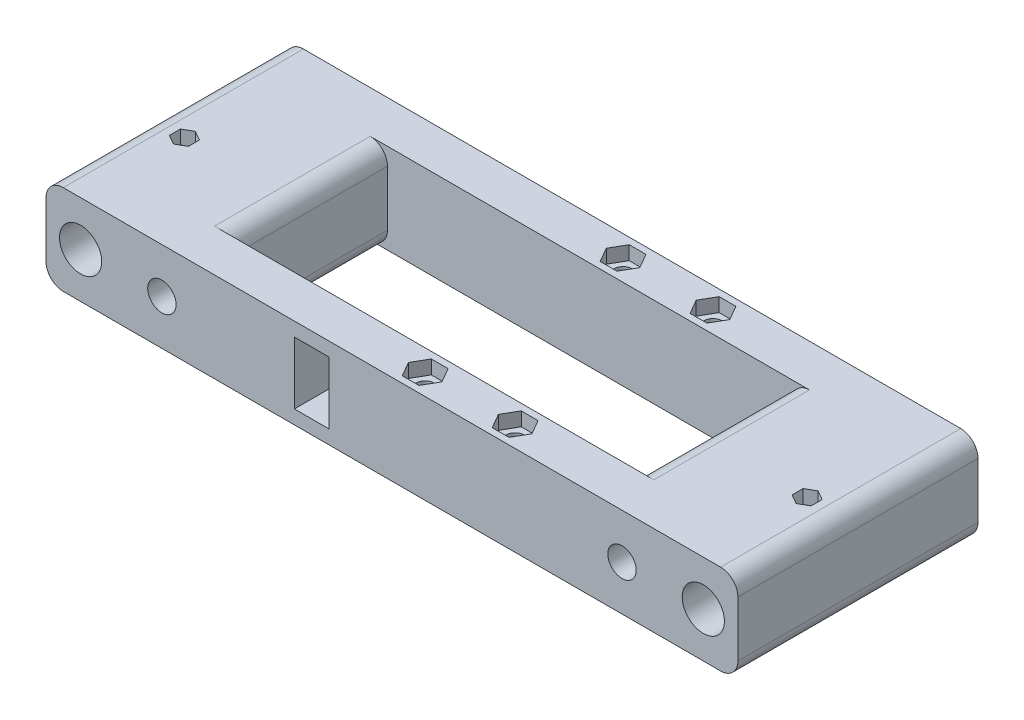
SolidWorks part; units mm, degrees
ref_plane "Front Plane" through (0, 0, 0) normal (0, 0, 1) x (1, 0, 0)
ref_plane "Top Plane" through (0, 0, 0) normal (0, 1, 0) x (1, 0, 0)
ref_plane "Right Plane" through (0, 0, 0) normal (1, 0, 0) x (0, 0, -1)
sketch "Sketch1" plane through (0, 0, 0) normal (0, 0, 1) x (1, 0, 0)
  line L0 (-58.5, 26) -> (-58.5, 0) construction
  line L1 (0, 0) -> (-100, 0)
  line L2 (0, 0) -> (0, 26)
  line L3 (0, 26) -> (-100, 26)
  line L4 (-100, 0) -> (-100, 26)
  circle A0 centre (-90, 13) radius 6.1
  circle A1 centre (-66.5, 13) radius 4.1
  point P9 (-100, 13)
  dimension "D3" = 12.2
  dimension "D4" = 8.2
  dimension "D1" = 100
  dimension "D2" = 26
  dimension "D5" = 23.5
  dimension "D6" = 10
  dimension "D7" = 8
  dimension "D8" = 41.5
extrude "Boss-Extrude1" add sketch "Sketch1" along normal blind 40
sketch "Sketch2" plane through (0, 0, 0) normal (0, 0, -1) x (-1, 0, 0)
  line L1 (100, 26) -> (0, 26)
  line L2 (100, 26) -> (100, 0)
  line L3 (100, 0) -> (0, 0)
  line L4 (0, 26) -> (0, 0)
extrude "Boss-Extrude2" add sketch "Sketch2" along normal blind 29.4
sketch "Sketch3" plane through (0, 26, 0) normal (0, 1, 0) x (1, 0, 0)
  line L0 (0, -40) -> (0, 29.4) construction
  line L1 (0, 17.2) -> (-58.5, 17.2)
  line L2 (0, 17.2) -> (0, -27.8)
  line L3 (0, -27.8) -> (-58.5, -27.8)
  line L4 (-58.5, 17.2) -> (-58.5, -27.8)
  line L5 (-100, -40) -> (-100, 29.4) construction
  line L6 (-100, 29.4) -> (0, 29.4) construction
  line L7 (0, -40) -> (-100, -40) construction
  dimension "D1" = 41.5
  dimension "D2" = 12.2
  dimension "D3" = 12.2
extrude "Cut-Extrude1" cut sketch "Sketch3" against normal up to next
mirror "Mirror2" about plane through (0, 0, 40) normal (-1, 0, 0) of "Boss-Extrude2", "Cut-Extrude1", "Boss-Extrude1"
sketch "Sketch4" plane through (0, 26, 0) normal (0, 1, 0) x (1, 0, 0)
  line L0 (-100, 29.4) -> (100, 29.4) construction
  line L1 (-5.5, 29.4) -> (-5.5, 17.2) construction
  line L2 (58.5, 17.2) -> (-58.5, 17.2) construction
  line L3 (58.5, 17.2) -> (58.5, -27.8) construction
  circle A0 centre (3.5, 23.3) radius 2.6
  circle A1 centre (29.5, 23.3) radius 2.6
  dimension "D1" = 6.1
  dimension "D3" = 9
  dimension "D4" = 26
  dimension "D5" = 5.2
  dimension "D2" = 64
extrude "Cut-Extrude2" cut sketch "Sketch4" against normal through all
sketch "Sketch5" plane through (0, 0, 0) normal (0, -1, 0) x (1, 0, 0)
  line L1 (34.2343, -23.3) -> (31.8671, -19.2)
  line L2 (31.8671, -19.2) -> (27.1329, -19.2)
  line L3 (27.1329, -19.2) -> (24.7657, -23.3)
  line L4 (24.7657, -23.3) -> (27.1329, -27.4)
  line L5 (27.1329, -27.4) -> (31.8671, -27.4)
  line L6 (31.8671, -27.4) -> (34.2343, -23.3)
  line L7 (-1.2343, -23.3) -> (1.1329, -27.4)
  line L8 (1.1329, -27.4) -> (5.8671, -27.4)
  line L9 (5.8671, -27.4) -> (8.2343, -23.3)
  line L10 (8.2343, -23.3) -> (5.8671, -19.2)
  line L11 (5.8671, -19.2) -> (1.1329, -19.2)
  line L12 (1.1329, -19.2) -> (-1.2343, -23.3)
  circle A0 centre (29.5, -23.3) radius 4.1 construction
  circle A1 centre (3.5, -23.3) radius 4.1 construction
  dimension "D1" = 8.2
  dimension "D2" = 8.2
extrude "Cut-Extrude3" cut sketch "Sketch5" against normal blind 4
ref_plane "Plane1" through (0, 0, 5.3) normal (0, 0, 1) x (1, 0, 0)
mirror "Mirror3" about plane through (0, 0, 5.3) normal (0, 0, 1) of "Cut-Extrude3", "Cut-Extrude2"
sketch "Sketch6" plane through (0, 0, 40) normal (0, 0, 1) x (1, 0, 0)
  line L0 (-8.1, 26) -> (-8.1, 0) construction
  line L1 (100, 26) -> (-100, 26) construction
  line L2 (-100, 0) -> (100, 0) construction
  line L3 (0.9, 26) -> (0.9, 4) construction
  line L4 (-100, 26) -> (-100, 0) construction
  line L5 (-18.2, 22) -> (-28.2, 22)
  line L6 (-18.2, 22) -> (-18.2, 4)
  line L7 (-18.2, 4) -> (-28.2, 4)
  line L8 (-28.2, 22) -> (-28.2, 4)
  point P12 (-28.2, 13)
  point P15 (-100, 13)
  dimension "D1" = 9
  dimension "D2" = 10.1
  dimension "D3" = 10
  dimension "D4" = 18
extrude "Cut-Extrude4" cut sketch "Sketch6" against normal up to vertex (14 mm away) up to point (0, -58.5, 26)
fillet "Fillet1" radius 5 8 edges at (58.5, 0, 5.3) (-58.5, 0, 5.3) (58.5, 26, 5.3) (100, 0, 5.3) (100, 26, 5.3) (-100, 0, 5.3) (-100, 26, 5.3) (-58.5, 26, 5.3)
sketch "Sketch7" plane through (0, 26, 0) normal (0, 1, 0) x (1, 0, 0)
  line L0 (63.5, 17.2) -> (-63.5, 17.2) construction
  line L1 (8.3497, 23.3) -> (5.9249, 27.5)
  line L2 (5.9249, 27.5) -> (1.0751, 27.5)
  line L3 (1.0751, 27.5) -> (-1.3497, 23.3)
  line L4 (-1.3497, 23.3) -> (1.0751, 19.1)
  line L5 (1.0751, 19.1) -> (5.9249, 19.1)
  line L6 (5.9249, 19.1) -> (8.3497, 23.3)
  line L7 (34.3497, 23.3) -> (31.9249, 27.5)
  line L8 (31.9249, 27.5) -> (27.0751, 27.5)
  line L9 (27.0751, 27.5) -> (24.6503, 23.3)
  line L10 (24.6503, 23.3) -> (27.0751, 19.1)
  line L11 (27.0751, 19.1) -> (31.9249, 19.1)
  line L12 (31.9249, 19.1) -> (34.3497, 23.3)
  circle A0 centre (3.5, 23.3) radius 4.2 construction
  circle A1 centre (29.5, 23.3) radius 4.2 construction
  point P20 (29.5, 19.1)
  dimension "D1" = 8.4
  dimension "D2" = 8.4
extrude "Cut-Extrude5" cut sketch "Sketch7" against normal blind 4
mirror "Mirror4" about plane through (0, 0, 5.3) normal (0, 0, 1) of "Cut-Extrude5"
sketch "Sketch8" plane through (0, 4, 0) normal (0, -1, 0) x (1, 0, 0)
  line L0 (27.1329, 38) -> (31.8671, 38) construction
  line L1 (31.8671, 38) -> (34.2343, 33.9) construction
  line L2 (34.2343, 33.9) -> (31.8671, 29.8) construction
  line L3 (31.8671, 29.8) -> (27.1329, 29.8) construction
  line L4 (27.1329, 29.8) -> (24.7657, 33.9) construction
  line L5 (24.7657, 33.9) -> (27.1329, 38) construction
  line L6 (1.1329, 38) -> (5.8671, 38) construction
  line L7 (5.8671, 38) -> (8.2343, 33.9) construction
  line L8 (8.2343, 33.9) -> (5.8671, 29.8) construction
  line L9 (5.8671, 29.8) -> (1.1329, 29.8) construction
  line L10 (1.1329, 29.8) -> (-1.2343, 33.9) construction
  line L11 (-1.2343, 33.9) -> (1.1329, 38) construction
  line L12 (27.1329, 38) -> (31.8671, 38)
  line L13 (31.8671, 38) -> (34.2343, 33.9)
  line L14 (34.2343, 33.9) -> (31.8671, 29.8)
  line L15 (31.8671, 29.8) -> (27.1329, 29.8)
  line L16 (27.1329, 29.8) -> (24.7657, 33.9)
  line L17 (24.7657, 33.9) -> (27.1329, 38)
  line L18 (1.1329, 38) -> (5.8671, 38)
  line L19 (5.8671, 38) -> (8.2343, 33.9)
  line L20 (8.2343, 33.9) -> (5.8671, 29.8)
  line L21 (5.8671, 29.8) -> (1.1329, 29.8)
  line L22 (1.1329, 29.8) -> (-1.2343, 33.9)
  line L23 (-1.2343, 33.9) -> (1.1329, 38)
  circle A0 centre (3.5, 33.9) radius 2.6 construction
  circle A1 centre (29.5, 33.9) radius 2.6 construction
  circle A2 centre (3.5, 33.9) radius 2.6
  circle A3 centre (29.5, 33.9) radius 2.6
extrude "Boss-Extrude3" add sketch "Sketch8" along normal up to surface (4 mm away) up to face at (3.5, 0, 33.9)
sketch "Sketch9" plane through (0, 4, 0) normal (0, -1, 0) x (1, 0, 0)
  line L0 (31.8671, -19.2) -> (27.1329, -19.2) construction
  line L1 (34.2343, -23.3) -> (31.8671, -19.2) construction
  line L2 (31.8671, -27.4) -> (34.2343, -23.3) construction
  line L3 (27.1329, -27.4) -> (31.8671, -27.4) construction
  line L4 (24.7657, -23.3) -> (27.1329, -27.4) construction
  line L5 (27.1329, -19.2) -> (24.7657, -23.3) construction
  line L6 (1.1329, -19.2) -> (-1.2343, -23.3) construction
  line L7 (5.8671, -19.2) -> (1.1329, -19.2) construction
  line L8 (8.2343, -23.3) -> (5.8671, -19.2) construction
  line L9 (5.8671, -27.4) -> (8.2343, -23.3) construction
  line L10 (1.1329, -27.4) -> (5.8671, -27.4) construction
  line L11 (-1.2343, -23.3) -> (1.1329, -27.4) construction
  line L12 (31.8671, -19.2) -> (27.1329, -19.2)
  line L13 (34.2343, -23.3) -> (31.8671, -19.2)
  line L14 (31.8671, -27.4) -> (34.2343, -23.3)
  line L15 (27.1329, -27.4) -> (31.8671, -27.4)
  line L16 (24.7657, -23.3) -> (27.1329, -27.4)
  line L17 (27.1329, -19.2) -> (24.7657, -23.3)
  line L18 (1.1329, -19.2) -> (-1.2343, -23.3)
  line L19 (5.8671, -19.2) -> (1.1329, -19.2)
  line L20 (8.2343, -23.3) -> (5.8671, -19.2)
  line L21 (5.8671, -27.4) -> (8.2343, -23.3)
  line L22 (1.1329, -27.4) -> (5.8671, -27.4)
  line L23 (-1.2343, -23.3) -> (1.1329, -27.4)
  circle A0 centre (3.5, -23.3) radius 2.6 construction
  circle A1 centre (29.5, -23.3) radius 2.6 construction
  circle A2 centre (3.5, -23.3) radius 2.6
  circle A3 centre (29.5, -23.3) radius 2.6
extrude "Boss-Extrude4" add sketch "Sketch9" along normal up to surface (4 mm away) up to face at (29.5, 0, -23.3)
sketch "Sketch10" plane through (0, 0, 0) normal (0, -1, 0) x (1, 0, 0)
  line L1 (-96.1, 0) -> (-83.9, 0) construction
  line L2 (83.9, 0) -> (96.1, 0) construction
  circle A0 centre (-90, 10) radius 1.5
  circle A1 centre (90, 10) radius 1.5
  point P4 (0, 0)
  point P5 (-90, 0)
  point P14 (90, 0)
  dimension "D3" = 3
  dimension "D4" = 3
  dimension "D1" = 10
  dimension "D2" = 10
extrude "Cut-Extrude6" cut sketch "Sketch10" against normal through all
sketch "Sketch11" plane through (0, 26, 0) normal (0, 1, 0) x (1, 0, 0)
  line L0 (-95, 29.4) -> (-95, -40) construction
  line L1 (-90, -13.1754) -> (-87.25, -11.5877)
  line L2 (-87.25, -11.5877) -> (-87.25, -8.4123)
  line L3 (-87.25, -8.4123) -> (-90, -6.8246)
  line L4 (-90, -6.8246) -> (-92.75, -8.4123)
  line L5 (-92.75, -8.4123) -> (-92.75, -11.5877)
  line L6 (-92.75, -11.5877) -> (-90, -13.1754)
  line L7 (90, -13.1754) -> (92.75, -11.5877)
  line L8 (92.75, -11.5877) -> (92.75, -8.4123)
  line L9 (92.75, -8.4123) -> (90, -6.8246)
  line L10 (90, -6.8246) -> (87.25, -8.4123)
  line L11 (87.25, -8.4123) -> (87.25, -11.5877)
  line L12 (87.25, -11.5877) -> (90, -13.1754)
  line L13 (95, -40) -> (95, 29.4) construction
  circle A0 centre (-90, -10) radius 2.75 construction
  circle A1 centre (90, -10) radius 2.75 construction
  point P10 (92.75, -10)
  dimension "D1" = 5.5
  dimension "D2" = 5.5
extrude "Cut-Extrude7" cut sketch "Sketch11" against normal blind 4
